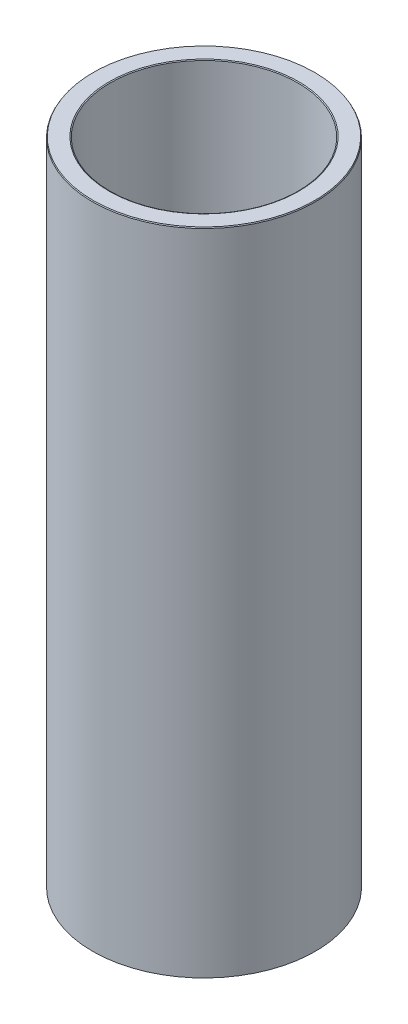
SolidWorks part; units mm, degrees
ref_plane "Front Plane" through (0, 0, 0) normal (0, 0, 1) x (1, 0, 0)
ref_plane "Top Plane" through (0, 0, 0) normal (0, 1, 0) x (1, 0, 0)
ref_plane "Right Plane" through (0, 0, 0) normal (1, 0, 0) x (0, 0, -1)
sketch "Sketch1" plane through (0, 0, 0) normal (0, 1, 0) x (1, 0, 0)
  circle A0 centre (0, 0) radius 47.5
  dimension "SLEEVE_OD" = 95
extrude "Boss-Extrude1" add sketch "Sketch1" along normal blind 277.4171
sketch "Sketch2" plane through (0, 0, 0) normal (0, 1, 0) x (1, 0, 0)
  circle A0 centre (0, 0) radius 40.0372
  dimension "BORE_D" = 80.0744
extrude "Cut-Extrude1" cut sketch "Sketch2" along normal through all
chamfer "Chamfer1" distance 0.4127 angle 30 4 edges at (0, 277.4171, 40.0372) (0, 0, 40.0372) (0, 0, 47.5) (0, 277.4171, 47.5) first distance on face at (0, 277.4171, 40.0372) first distance on face at (0, 0, 40.0372) first distance on face at (0, 277.4171, 47.5)
